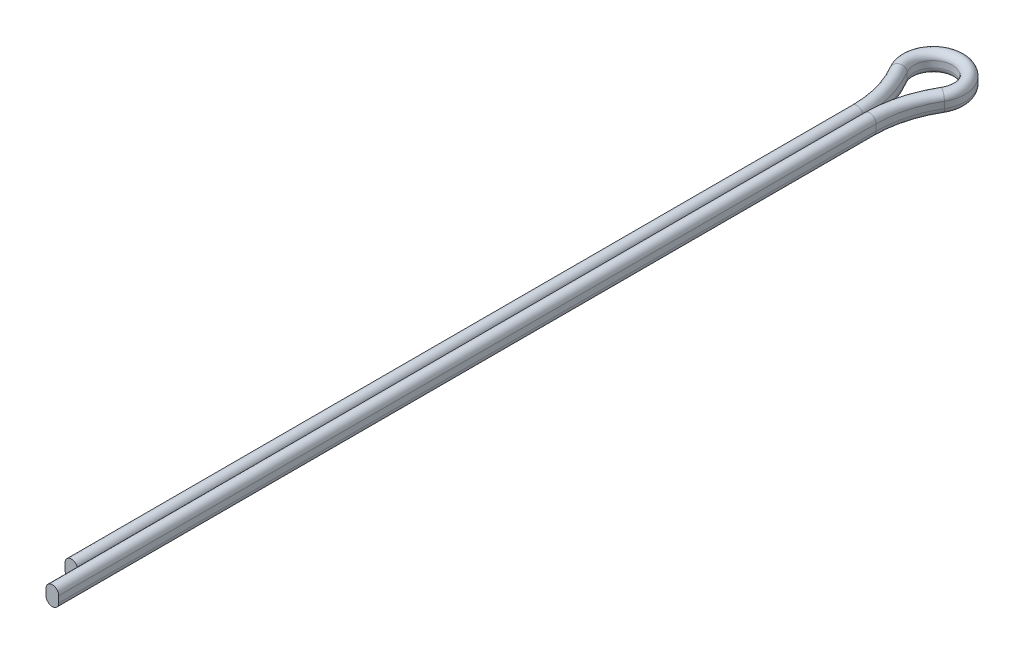
SolidWorks part; units mm, degrees
material "AISI 304"
ref_plane "Front Plane" through (0, 0, 0) normal (0, 0, 1) x (1, 0, 0)
ref_plane "Top Plane" through (0, 0, 0) normal (0, 1, 0) x (1, 0, 0)
ref_plane "Right Plane" through (0, 0, 0) normal (1, 0, 0) x (0, 0, -1)
sketch "Sketch1" plane through (0, 0, 0) normal (0, 1, 0) x (1, 0, 0)
  line L0 (-0.4, 2) -> (-0.4, 51.5)
  line L1 (0.4, 51.5) -> (0.4, 0)
  arc A0 (-1.3785, 55.0877) -> (1.3785, 55.0877) centre (0, 55.9) cw
  arc A1 (-0.4, 51.5) -> (-1.3785, 55.0877) centre (-7.4667, 51.5) ccw
  arc A2 (1.3785, 55.0877) -> (0.4, 51.5) centre (7.4667, 51.5) ccw
  point P10 (0, 57.5)
  dimension "D5" = 1.6
  dimension "D1" = 0.8
  dimension "D2" = 57.5
  dimension "D3" = 2
  dimension "D4" = 6
sketch "Sketch2" plane through (0, 0, 0) normal (0, 0, 1) x (1, 0, 0)
  line L2 (0.4, -0.2) -> (0.4, 0.2) construction
  line L3 (1.6, 0) -> (-1.6, 0) construction
  line L4 (1.3785, 0) -> (0.4, 0) construction
  line L5 (0, -0.2) -> (0, 0.2)
  line L6 (0.8, -0.2) -> (0.8, 0.2)
  arc A0 (0, -0.2) -> (0.8, -0.2) centre (0.4, -0.2) ccw
  arc A1 (0.8, 0.2) -> (0, 0.2) centre (0.4, 0.2) ccw
  point P6 (0.4, 0)
  point P12 (0.4, 0.6)
  point P13 (0.4, -0.6)
  dimension "D1" = 0.4
  dimension "D2" = 1.2
sweep "Sweep1" add profiles "Sketch2" path "Sketch1"
ref_axis "Axis1" through (0, 0, -59.395) along (0, 0, 1)
